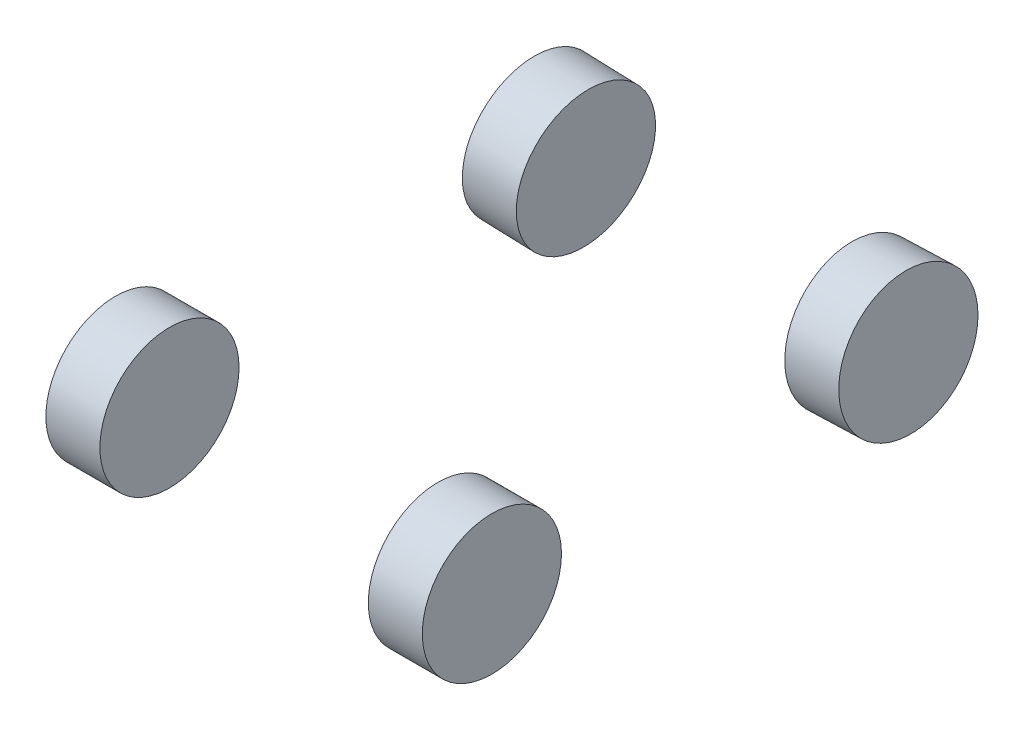
SolidWorks part; units mm, degrees
ref_plane "Front Plane" through (0, 0, 0) normal (0, 0, 1) x (1, 0, 0)
ref_plane "Top Plane" through (0, 0, 0) normal (0, 1, 0) x (1, 0, 0)
ref_plane "Right Plane" through (0, 0, 0) normal (1, 0, 0) x (0, 0, -1)
sketch3d "3DSketch1"
  line L0 (-519.3255, 235, 2080) -> (-681.2452, 235, 2080) construction
  line L1 (-681.2452, 235, 2080) -> (-684.2452, 235, 2080) construction
  line L2 (-519.3255, 235, 2080) -> (-412.1048, 235, 2080) construction
  line L3 (-600, 235, 2080) -> (-600, 494, 2080) construction
  line L4 (-600, 235, 2080) -> (-600, 235, 2339) construction
  line L5 (-600, 235, 2080) -> (-600, 235, 2339) construction
  line L6 (-600, 235, 2080) -> (-600, -24, 2080) construction
  arc A0 (-681.2452, 468.1652, 2050.6914) -> (-681.2452, 1.8348, 2109.3086) centre (-681.2452, 235, 2080) ccw construction
  arc A1 (-681.2452, 468.1652, 2050.6914) -> (-681.2452, 1.8348, 2109.3086) centre (-681.2452, 235, 2080) ccw construction
  arc A2 (-519.3255, 468.1652, 2050.6914) -> (-519.3255, 1.8348, 2109.3086) centre (-519.3255, 235, 2080) ccw construction
  arc A3 (-519.3255, 468.1652, 2050.6914) -> (-519.3255, 1.8348, 2109.3086) centre (-519.3255, 235, 2080) ccw construction
  arc A4 (-681.2452, 1.8348, 2109.3086) -> (-681.2452, 468.1652, 2050.6914) centre (-681.2452, 235, 2080) ccw construction
  arc A5 (-681.2452, 1.8348, 2109.3086) -> (-681.2452, 468.1652, 2050.6914) centre (-681.2452, 235, 2080) ccw construction
  arc A6 (-519.3255, 1.8348, 2109.3086) -> (-519.3255, 468.1652, 2050.6914) centre (-519.3255, 235, 2080) ccw construction
  arc A7 (-519.3255, 1.8348, 2109.3086) -> (-519.3255, 468.1652, 2050.6914) centre (-519.3255, 235, 2080) ccw construction
  circle A10 centre (-600, 235, 2080) radius 259
  point P3 (-916.2452, 235, 2080)
  point P4 (-916.2452, 235, 2080)
  point P8 (-754.3255, 235, 2080)
  point P9 (-754.3255, 235, 2080)
  point P13 (-916.2452, 235, 2080)
  point P14 (-916.2452, 235, 2080)
  point P16 (-754.3255, 235, 2080)
  point P17 (-754.3255, 235, 2080)
  point P22 (-341, 235, 2080)
  dimension "D2" = 518
  dimension "D1" = 3
sketch3d "3DSketch2"
  line L0 (-519.1248, 232.1758, 530) -> (-680.9459, 237.8267, 530) construction
  line L1 (-600.0354, 235.0012, 530) -> (-600.0354, 235.0012, 789) construction
  line L2 (-600.0354, 235.0012, 530) -> (-609.0743, -23.841, 530) construction
  line L3 (-600.0354, 235.0012, 530) -> (-600.0354, 235.0012, 271) construction
  arc A0 (-672.8078, 470.8721, 500.8691) -> (-689.084, 4.7813, 559.1309) centre (-680.9459, 237.8267, 530) ccw construction
  arc A1 (-689.084, 4.7813, 559.1309) -> (-672.8078, 470.8721, 500.8691) centre (-680.9459, 237.8267, 530) ccw construction
  arc A2 (-527.2629, -0.8696, 559.1309) -> (-510.9867, 465.2212, 500.8691) centre (-519.1248, 232.1758, 530) ccw construction
  arc A3 (-510.9867, 465.2212, 500.8691) -> (-527.2629, -0.8696, 559.1309) centre (-519.1248, 232.1758, 530) ccw construction
  arc A4 (-672.8078, 470.8721, 500.8691) -> (-689.084, 4.7813, 559.1309) centre (-680.9459, 237.8267, 530) ccw construction
  arc A5 (-689.084, 4.7813, 559.1309) -> (-672.8078, 470.8721, 500.8691) centre (-680.9459, 237.8267, 530) ccw construction
  arc A6 (-527.2629, -0.8696, 559.1309) -> (-510.9867, 465.2212, 500.8691) centre (-519.1248, 232.1758, 530) ccw construction
  arc A7 (-510.9867, 465.2212, 500.8691) -> (-527.2629, -0.8696, 559.1309) centre (-519.1248, 232.1758, 530) ccw construction
  circle A10 centre (-600.0354, 235.0012, 530) radius 259
  point P3 (-915.8027, 246.0281, 530)
  point P5 (-915.8027, 246.0281, 530)
  point P6 (-915.8027, 246.0281, 530)
  point P7 (-915.8027, 246.0281, 530)
  point P11 (-753.9817, 240.3772, 530)
  point P13 (-753.9817, 240.3772, 530)
  point P14 (-753.9817, 240.3772, 530)
  point P15 (-753.9817, 240.3772, 530)
  point P16 (-599.7502, 234.9913, 530)
  point P19 (-341.1931, 225.9623, 530)
  point P20 (-600.0354, 235.0012, 789)
  point P22 (-609.0743, -23.841, 530)
  dimension "D1" = 518
ref_plane "Plane1" through (-526.5904, 18.3889, 0) normal (-0.9994, 0.0349, 0) x (0, 0, 1)
extrude "Boss-Extrude2" add sketch "3DSketch2" along direction (-0.9994, 0.0349, 0) on the side of the normal blind 100.5 and the other way blind 100.5 separate body
ref_plane "Plane2" through (-519.3255, 0, 0) normal (-1, 0, 0) x (0, 0, 1)
extrude "Boss-Extrude3" add sketch "3DSketch1" along direction (-1, 0, 0) on the side of the normal blind 100.5 and the other way blind 100.5 separate body
mirror "Mirror1" about plane through (0, 0, 0) normal (1, 0, 0) of bodies 102 103
